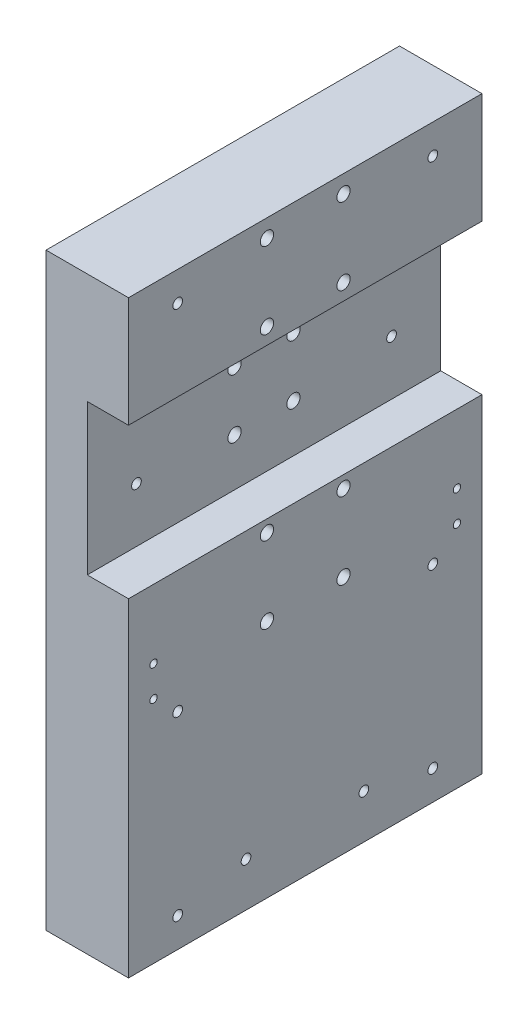
SolidWorks part; units mm, degrees
ref_plane "Front Plane" through (0, 0, 0) normal (0, 0, 1) x (1, 0, 0)
ref_plane "Top Plane" through (0, 0, 0) normal (0, 1, 0) x (1, 0, 0)
ref_plane "Right Plane" through (0, 0, 0) normal (1, 0, 0) x (0, 0, -1)
sketch "Sketch1" plane through (0, 0, 0) normal (0, 0, 1) x (1, 0, 0)
  line L0 (0, 0) -> (0, 200)
  line L1 (0, 200) -> (28, 200)
  line L2 (28, 200) -> (28, 162.5)
  line L3 (14, 162.5) -> (14, 111.5)
  line L4 (14, 162.5) -> (28, 162.5)
  line L5 (14, 111.5) -> (28, 111.5)
  line L6 (28, 111.5) -> (28, 0)
  line L7 (28, 0) -> (0, 0)
  line L8 (-49.525, 137) -> (95.9642, 137) construction
  point P12 (14, 137)
  dimension "D1" = 200
  dimension "D2" = 25.5
  dimension "D4" = 28
  dimension "D6" = 63
extrude "Boss-Extrude1" add sketch "Sketch1" along normal blind 120 contours L0 L1 L2 L4 L3 L5 L6 L7
sketch "Sketch2" plane through (0, 0, 0) normal (-1, 0, 0) x (0, 0, 1)
  line L0 (60, 200) -> (60, 0) construction
  line L1 (120, 200) -> (0, 200) construction
  line L2 (120, 0) -> (0, 0) construction
  point P6 (73, 194)
  point P7 (73, 168)
  point P8 (70, 147.7)
  point P9 (70, 127.7)
  point P10 (73, 107.4)
  point P11 (73, 81.4)
  point P12 (47, 81.4)
  point P13 (47, 107.4)
  point P14 (50, 127.7)
  point P15 (50, 147.7)
  point P16 (47, 168)
  point P17 (47, 194)
  dimension "D1" = 6
  dimension "D2" = 26
  dimension "D3" = 46.3
  dimension "D4" = 20
  dimension "D5" = 20.3
  dimension "D6" = 26
  dimension "D7" = 13
  dimension "D8" = 10
hole_wizard "CBORE for M4 SHCS4" positions "3DSketch2" profile "Sketch4" counterbore size "M4" standard "ANSI Metric" end condition through all
sketch3d "3DSketch2"
  point P0 (0, 194, 73)
  point P3 (0, 168, 73)
  point P6 (0, 147.7, 70)
  point P9 (0, 127.7, 70)
  point P12 (0, 107.4, 73)
  point P15 (0, 81.4, 73)
  point P18 (0, 81.4, 47)
  point P21 (0, 107.4, 47)
  point P24 (0, 127.7, 50)
  point P27 (0, 147.7, 50)
  point P30 (0, 168, 47)
  point P33 (0, 194, 47)
sketch "Sketch4" plane through (0, 194, 73) normal (0, 1, 0) x (0, 0, 1)
  line L0 (0, 0) -> (0, 28)
  line L1 (0, 28) -> (2.25, 28)
  line L3 (2.25, 28) -> (2.25, 4)
  line L4 (2.25, 4) -> (4, 4)
  line L5 (4, 4) -> (4, 0)
  line L7 (4, 0) -> (0, 0)
  line L11 (0, -6.35) -> (0, 107.95) construction
  dimension "Thru Hole Dia." = 4.5
  dimension "Thru Hole Depth" = 28
  dimension "C'Bore Dia." = 8
  dimension "C'Bore Depth" = 4
sketch "Sketch5" plane through (0, 0, 0) normal (-1, 0, 0) x (0, 0, 1)
  line L0 (16.7, 200) -> (16.7, 0) construction
  line L1 (120, 200) -> (0, 200) construction
  line L2 (120, 0) -> (0, 0) construction
  line L3 (60, 200) -> (60, 0) construction
  line L4 (60, 200) -> (60, 0) construction
  line L5 (103.3, 200) -> (103.3, 0) construction
  point P12 (16.7, 190)
  point P13 (103.3, 10)
  point P14 (16.7, 130)
  point P15 (16.7, 70)
  point P16 (16.7, 10)
  point P17 (103.3, 70)
  point P18 (103.3, 130)
  point P19 (103.3, 190)
  dimension "D1" = 43.3
  dimension "D2" = 10
  dimension "D3" = 4
hole_wizard "M4 Tapped Hole1" positions "3DSketch3" profile "Sketch6" tap size "M4" standard "ISO" end condition through all
sketch3d "3DSketch3"
  point P0 (0, 190, 16.7)
  point P3 (0, 130, 16.7)
  point P6 (0, 70, 16.7)
  point P9 (0, 10, 16.7)
  point P12 (0, 10, 103.3)
  point P15 (0, 70, 103.3)
  point P18 (0, 130, 103.3)
  point P21 (0, 190, 103.3)
sketch "Sketch6" plane through (0, 190, 16.7) normal (0, 1, 0) x (0, 0, 1)
  line L0 (0, 0) -> (0, 28)
  line L1 (0, 28) -> (1.65, 28)
  line L2 (1.65, 28) -> (1.65, 0)
  line L5 (1.65, 0) -> (0, 0)
  line L11 (0, -6.35) -> (0, 107.95) construction
  dimension "Thread Major Dia." = 3.3
  dimension "Thru Tap Drill Depth" = 28
ref_plane "Plane1" through (0, 0, 60) normal (0, 0, -1) x (-1, 0, 0)
sketch "Sketch7" plane through (0, 0, 0) normal (0, -1, 0) x (1, 0, 0)
  line L0 (14, 120) -> (14, 0) construction
  line L1 (28, 120) -> (0, 120) construction
  line L2 (28, 0) -> (0, 0) construction
  line L3 (28, 60) -> (0, 60) construction
  line L4 (28, 120) -> (28, 0) construction
  line L5 (0, 120) -> (0, 0) construction
  point P12 (14, 60)
  point P13 (14, 90)
  point P14 (14, 30)
  dimension "D1" = 30
hole_wizard "M5 Tapped Hole1" positions "3DSketch4" profile "Sketch8" tap size "M5" standard "ISO"
sketch3d "3DSketch4"
  point P0 (14, 0, 90)
  point P3 (14, 0, 60)
  point P6 (14, 0, 30)
sketch "Sketch8" plane through (14, 0, 90) normal (1, 0, 0) x (0, 0, -1)
  line L0 (0, 0) -> (0, 18.6618)
  line L1 (0, 18.6618) -> (2.1, 17.4)
  line L2 (2.1, 17.4) -> (2.1, 0)
  line L5 (2.1, 0) -> (0, 0)
  line L10 (0, 18.6618) -> (-2.1, 17.4) construction
  line L11 (0, -6.35) -> (0, 107.95) construction
  dimension "Tap Drill Dia." = 4.2
  dimension "Tap Drill Depth" = 17.4
  dimension "Drill Angle" = 118
sketch "Sketch9" plane through (28, 0, 0) normal (1, 0, 0) x (0, 0, -1)
  line L0 (-40.1, 23.78) -> (-40.1, 0) construction
  line L1 (-80.1, 23.78) -> (-80.1, 0) construction
  line L8 (-120, 0) -> (0, 0) construction
  line L11 (-120, 0) -> (0, 0) construction
  point P8 (-40.1, 15)
  point P9 (-80.1, 15)
  dimension "D1" = 15
hole_wizard "M4 Tapped Hole2" positions "3DSketch5" profile "Sketch10" tap size "M4" standard "ISO" end condition through all
sketch3d "3DSketch5"
  point P0 (28, 15, 80.1)
  point P3 (28, 15, 40.1)
sketch "Sketch10" plane through (28, 15, 80.1) normal (0, 1, 0) x (0, 0, -1)
  line L0 (0, 0) -> (0, 28)
  line L1 (0, 28) -> (1.65, 28)
  line L2 (1.65, 28) -> (1.65, 0)
  line L5 (1.65, 0) -> (0, 0)
  line L11 (0, -6.35) -> (0, 107.95) construction
  dimension "Thread Major Dia." = 3.3
  dimension "Thru Tap Drill Depth" = 28
sketch "Sketch11" plane through (28, 0, 0) normal (1, 0, 0) x (0, 0, -1)
  line L0 (-60, 0) -> (-60, 200) construction
  point P0 (-8.5, 77.775)
  point P1 (-8.5, 88.175)
  point P8 (-111.5, 77.775)
  point P9 (-111.5, 88.175)
hole_wizard "M3 Tapped Hole1" positions "3DSketch9" profile "Sketch15" tap size "M3" standard "ISO"
sketch3d "3DSketch9"
  point P0 (28, 88.175, 8.5)
  point P3 (28, 77.775, 8.5)
  point P7 (28, 88.175, 111.5)
  point P10 (28, 77.775, 111.5)
sketch "Sketch15" plane through (28, 88.175, 8.5) normal (0, 1, 0) x (0, 0, -1)
  line L0 (0, 0) -> (0, 8.2511)
  line L1 (0, 8.2511) -> (1.25, 7.5)
  line L2 (1.25, 7.5) -> (1.25, 0)
  line L5 (1.25, 0) -> (0, 0)
  line L10 (0, 8.2511) -> (-1.25, 7.5) construction
  line L11 (0, -6.35) -> (0, 107.95) construction
  dimension "Tap Drill Dia." = 2.5
  dimension "Tap Drill Depth" = 7.5
  dimension "Drill Angle" = 118
